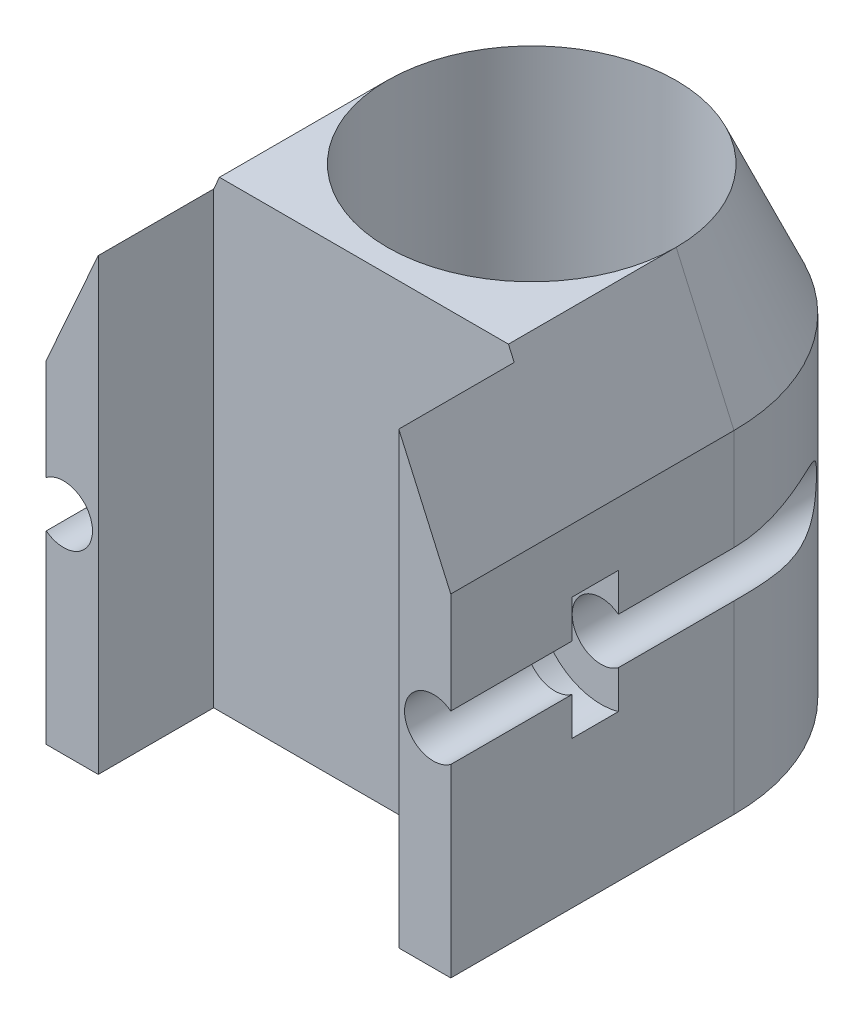
SolidWorks part; units mm, degrees
ref_plane "Alzado" through (0, 0, 0) normal (0, 0, 1) x (1, 0, 0)
ref_plane "Planta" through (0, 0, 0) normal (0, 1, 0) x (1, 0, 0)
ref_plane "Vista lateral" through (0, 0, 0) normal (1, 0, 0) x (0, 0, -1)
sketch "Croquis1" plane through (0, 0, 0) normal (0, 1, 0) x (1, 0, 0)
  circle A0 centre (0, 0) radius 12.5
  circle A1 centre (0, 0) radius 17.5
  dimension "D1" = 25
  dimension "D2" = 5
extrude "Saliente-Extruir1" add sketch "Croquis1" along normal blind 40
sketch "Croquis2" plane through (0, 0, 0) normal (0, 0, 1) x (1, 0, 0)
  line L0 (0, -19.25) -> (0, 19.25) construction
  line L1 (-17.5, 0) -> (17.5, 0)
  line L2 (-17.5, 0) -> (-17.5, 40)
  line L3 (-17.5, 40) -> (17.5, 40)
  line L4 (17.5, 0) -> (17.5, 40)
  line L5 (-17.5, 0) -> (17.5, 40) construction
  line L6 (-17.5, 40) -> (17.5, 0) construction
  point P0 (0, 20)
extrude "Saliente-Extruir2" add sketch "Croquis2" along normal blind 30
sketch "Croquis3" plane through (0, 40, 0) normal (0, 1, 0) x (1, 0, 0)
  circle A0 centre (0, 0) radius 12.5
extrude "Cortar-Extruir1" cut sketch "Croquis3" against normal blind 55
sketch "Croquis4" plane through (0, 40, 0) normal (0, 1, 0) x (1, 0, 0)
  line L0 (0, -22) -> (0, 22) construction
  line L1 (-13, -24.5128) -> (13, -24.5128)
  line L2 (-13, -24.5128) -> (-13, -14.5128)
  line L3 (-13, -14.5128) -> (13, -14.5128)
  line L4 (13, -24.5128) -> (13, -14.5128)
  line L5 (-13, -24.5128) -> (13, -14.5128) construction
  line L6 (-13, -14.5128) -> (13, -24.5128) construction
  point P0 (0, -19.5128)
  dimension "D1" = 10
  dimension "D2" = 26
extrude "Cortar-Extruir2" cut sketch "Croquis4" against normal blind 55
sketch "Croquis5" plane through (0, 0, 30) normal (0, 0, 1) x (1, 0, 0)
  line L0 (0, -22) -> (0, 22) construction
  line L1 (17.5, 40) -> (-17.5, 40) construction
  circle A0 centre (16, 18) radius 2.5
  circle A1 centre (-16, 18) radius 2.5
  dimension "D1" = 5
  dimension "D2" = 5
  dimension "D3" = 32
  dimension "D4" = 16
  dimension "D5" = 22
extrude "Cortar-Extruir3" cut sketch "Croquis5" against normal blind 55
chamfer "Chaflán1" distance 5 angle 66 3 edges at (17.5, 40, 15) (-17.5, 40, 15) (0, 40, -17.5) first distance on face at (0, 40, 19.5128)
sketch "Croquis6" plane through (0, 0, 30) normal (0, 0, 1) x (1, 0, 0)
  line L0 (0, -22) -> (0, 22) construction
  line L1 (-21.6873, -1.8941) -> (21.6873, -1.8941)
  line L2 (-21.6873, -1.8941) -> (-21.6873, 42.5442)
  line L3 (-21.6873, 42.5442) -> (21.6873, 42.5442)
  line L4 (21.6873, -1.8941) -> (21.6873, 42.5442)
  line L5 (-21.6873, -1.8941) -> (21.6873, 42.5442) construction
  line L6 (-21.6873, 42.5442) -> (21.6873, -1.8941) construction
  point P0 (0, 20.325)
extrude "Cortar-Extruir4" cut sketch "Croquis6" against normal blind 5.5 contours L3 L4 L1 L2
ref_plane "Plano3" through (0, 0, 14) normal (0, 0, 1) x (1, 0, 0)
sketch "Croquis7" plane through (0, 0, 14) normal (0, 0, 1) x (1, 0, 0)
  circle A0 centre (-16, 18) radius 5.5
  dimension "D1" = 11
extrude "Cortar-Extruir5" cut sketch "Croquis7" against normal blind 4
mirror "Simetría1" about plane through (0, 0, 0) normal (1, 0, 0) of "Cortar-Extruir5"
